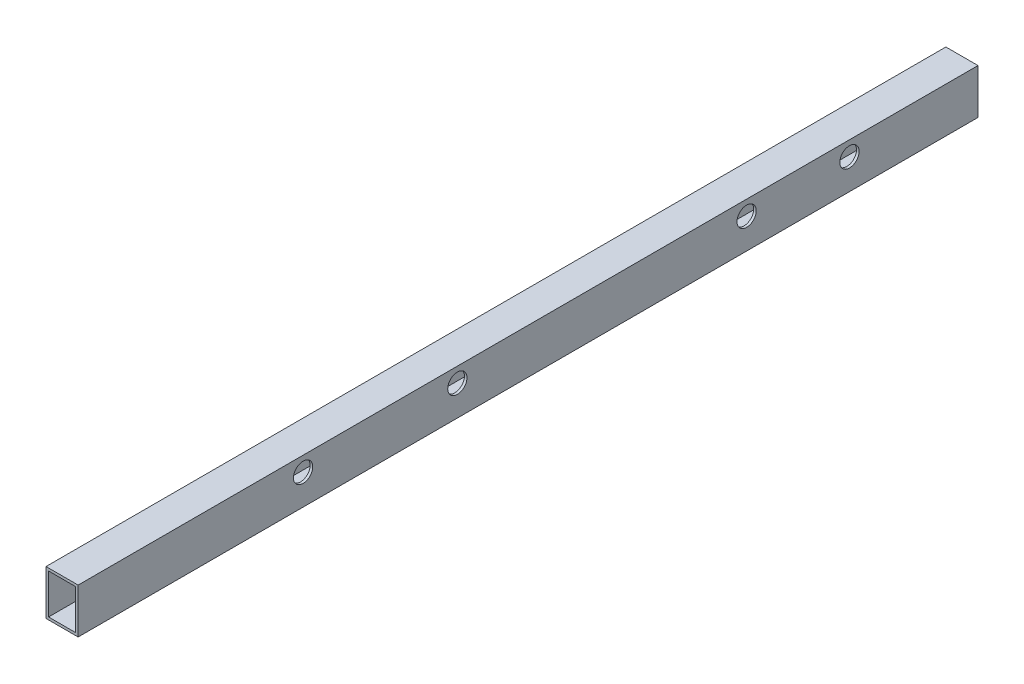
SolidWorks part; units mm, degrees
ref_plane "Front Plane" through (0, 0, 0) normal (0, 0, 1) x (1, 0, 0)
ref_plane "Top Plane" through (0, 0, 0) normal (0, 1, 0) x (1, 0, 0)
ref_plane "Right Plane" through (0, 0, 0) normal (1, 0, 0) x (0, 0, -1)
sketch "Sketch1" plane through (0, 0, 0) normal (0, 0, 1) x (1, 0, 0)
  line L1 (0, 0) -> (50, 0)
  line L2 (0, 0) -> (0, -70)
  line L3 (0, -70) -> (50, -70)
  line L4 (50, 0) -> (50, -70)
  line L5 (4, -4) -> (46, -4)
  line L6 (4, -4) -> (4, -66)
  line L7 (4, -66) -> (46, -66)
  line L8 (46, -4) -> (46, -66)
  dimension "D1" = 70
  dimension "D2" = 50
  dimension "D3" = 4
  dimension "D4" = 4
  dimension "D5" = 4
  dimension "D6" = 4
extrude "Boss-Extrude2" add sketch "Sketch1" along normal blind 1400
sketch "Sketch2" plane through (50, 0, 0) normal (1, 0, 0) x (0, 0, -1)
  line L0 (-1400, -70) -> (-1400, 0) construction
  line L1 (-1400, 0) -> (0, 0) construction
  circle A0 centre (-1050, -23) radius 15
  circle A1 centre (-200, -23) radius 15
  circle A2 centre (-810, -23) radius 15
  circle A3 centre (-360, -23) radius 15
  dimension "D1" = 30
  dimension "D2" = 30
  dimension "D3" = 30
  dimension "D4" = 30
  dimension "D5" = 350
  dimension "D6" = 240
  dimension "D7" = 450
  dimension "D8" = 160
  dimension "D9" = 23
extrude "Cut-Extrude1" cut sketch "Sketch2" against normal through all
equation "\"D4@Sketch1\"=\"D3@Sketch1\""
equation "\"D5@Sketch1\"=\"D3@Sketch1\""
equation "\"D2@Sketch2\"=\"D1@Sketch2\""
